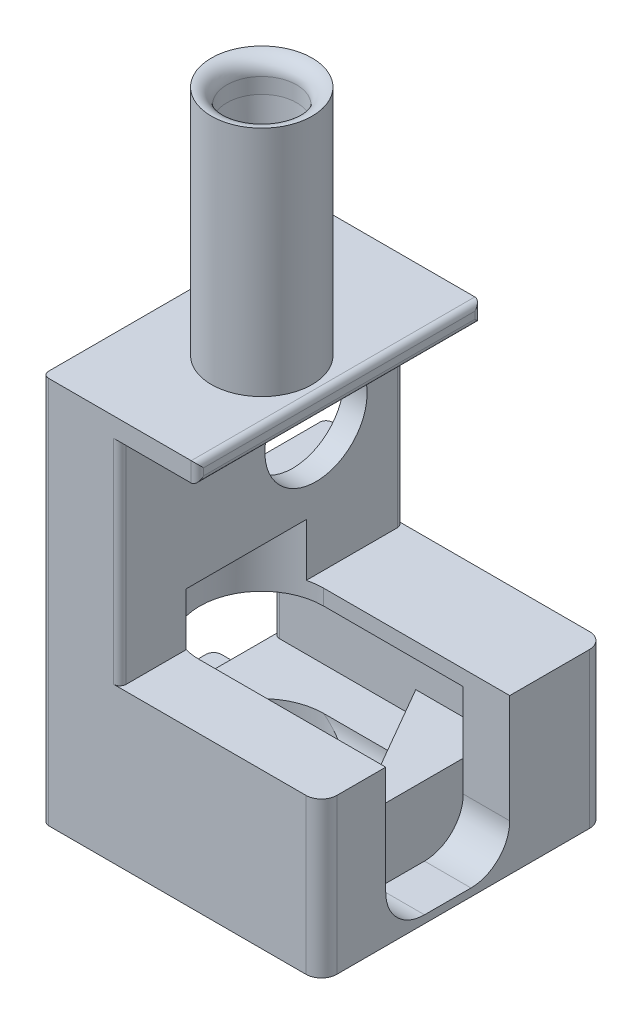
SolidWorks part; units mm, degrees
note: '?' marks a value the reader was unsure of.
ref_plane "Front Plane" through (0, 0, 0) normal (0, 0, 1) x (1, 0, 0)
ref_plane "Top Plane" through (0, 0, 0) normal (0, 1, 0) x (1, 0, 0)
ref_plane "Right Plane" through (0, 0, 0) normal (1, 0, 0) x (0, 0, -1)
sketch "Sketch1" plane through (0, 0, 0) normal (0, 1, 0) x (1, 0, 0)
  line L7 (-6, -6.5) -> (6, -6.5)
  line L8 (-6, -6.5) -> (-6, 6.5)
  line L9 (-6, 6.5) -> (6, 6.5)
  line L10 (6, -6.5) -> (6, 6.5)
  line L11 (-6, -6.5) -> (6, 6.5) construction
  line L12 (-6, 6.5) -> (6, -6.5) construction
  point P0 (0, 0)
  dimension "D1" = 12
  dimension "D3" = 13
extrude "Boss-Extrude1" add sketch "Sketch1" along normal blind 19
sketch "Sketch2" plane through (0, 0, 0) normal (0, -1, 0) x (1, 0, 0)
  circle A0 centre (0, 0) radius 4
  dimension "D1" = 8
extrude "Cut-Extrude1" cut sketch "Sketch2" against normal blind 16
ref_plane "Plane1" through (0, 2, 0) normal (0, -1, 0) x (-1, 0, 0)
sketch "Sketch3" plane through (0, 0, 0) normal (0, -1, 0) x (1, 0, 0)
  line L1 (6, 6.5) -> (6, -6.5) construction
  line L6 (6, -6.5) -> (-6, -6.5) construction
  line L10 (-6, -6.5) -> (-6, 6.5) construction
  line L11 (-6, 6.5) -> (6, 6.5) construction
  line L12 (6, 6.5) -> (6, -6.5)
  line L13 (6, -6.5) -> (-6, -6.5)
  line L14 (-6, -6.5) -> (-6, 6.5)
  line L15 (-6, 6.5) -> (6, 6.5)
extrude "Cut-Extrude2" cut sketch "Sketch3" against normal blind 6 from surface at -2 starting at plane "Plane1"
sketch "Sketch5" plane through (0, 19, 0) normal (0, 1, 0) x (1, 0, 0)
  line L0 (6, -6.5) -> (6, 6.5) construction
  line L1 (-6, -6.5) -> (6, -6.5)
  line L2 (-6, -6.5) -> (-6, 6.5)
  line L3 (-6, 6.5) -> (6, 6.5)
  line L4 (6, -6.5) -> (6, 6.5)
  line L5 (6, 6.5) -> (-6, 6.5) construction
extrude "Boss-Extrude2" add sketch "Sketch5" along normal blind 5
sketch "Sketch9" plane through (0, 24, 0) normal (0, 1, 0) x (1, 0, 0)
  circle A0 centre (0, 0) radius 1
  dimension "D1" = 2
fillet "Fillet1" radius 2 2 edges at (-6, 16, -6.5) (-6, 16, 6.5)
fillet "Fillet4" radius 2 2 edges at (-6, 1, -6.5) (-6, 1, 6.5)
ref_plane "Plane4" through (0, 0, 0) normal (0, 0, 1) x (1, 0, 0)
sketch "Sketch21" plane through (-6, 0, 0) normal (-1, 0, 0) x (0, 0, 1)
  line L0 (-4.5, 24) -> (-4.5, 8) construction
  line L1 (-4.5, 22) -> (-2, 22)
  line L2 (-4.5, 22) -> (-4.5, 14)
  line L3 (-4.5, 14) -> (-2, 14)
  line L4 (-2, 22) -> (-2, 14)
  line L5 (-4.5, 24) -> (4.5, 24) construction
  line L6 (0, 24) -> (0, 0) construction
  line L7 (-4.5, 0) -> (4.5, 0) construction
  line L8 (2, 22) -> (2, 14)
  line L9 (4.5, 14) -> (2, 14)
  line L10 (4.5, 22) -> (4.5, 14)
  line L11 (4.5, 22) -> (2, 22)
  line L12 (4.5, 8) -> (4.5, 24) construction
  line L13 (-4.5, 0) -> (4.5, 0)
  line L14 (-4.5, 0) -> (-4.5, 1.5)
  line L15 (-4.5, 1.5) -> (4.5, 1.5)
  line L16 (4.5, 0) -> (4.5, 1.5)
  line L17 (-4.5, 2) -> (-4.5, 0) construction
  line L18 (-4.5, 0) -> (4.5, 0) construction
  dimension "D1" = 2.5
  dimension "D2" = 2
  dimension "D3" = 8
  dimension "D4" = 1.5
extrude "Boss-Extrude4" add sketch "Sketch21" along normal blind 1.6
fillet "Fillet3" radius 0.5 4 edges at (-7.6, 22, 3.25) (-7.6, 18, 2) (-7.6, 14, 3.25) (-7.6, 18, 4.5)
fillet "Fillet7" radius 0.5 4 edges at (-7.6, 14, -3.25) (-7.6, 18, -4.5) (-7.6, 18, -2) (-7.6, 22, -3.25)
fillet "Fillet5" radius 0.5 2 edges at (-7.6, 0.75, -4.5) (-7.6, 0.75, 4.5)
sketch "Sketch23" plane through (0, 0, 0) normal (0, -1, 0) x (1, 0, 0)
  line L4 (-7.6, 4) -> (-7.6, -4)
  line L8 (-4, -6.5) -> (6, -6.5)
  line L9 (6, -6.5) -> (6, 6.5)
  line L10 (6, 6.5) -> (-4, 6.5)
  line L11 (-7.6, 4) -> (-7.6, -4)
  line L14 (-4, -6.5) -> (6, -6.5)
  line L15 (6, -6.5) -> (6, 6.5)
  line L16 (6, 6.5) -> (-4, 6.5)
  line L18 (-7.1, -4.5) -> (-6, -4.5)
  line L19 (-7.1, -4.5) -> (-6, -4.5)
  line L20 (-6, 4.5) -> (-7.1, 4.5)
  line L21 (-6, 4.5) -> (-7.1, 4.5)
  circle A0 centre (0, 0) radius 4 construction
  circle A1 centre (0, 0) radius 4
  arc A5 (-7.6, -4) -> (-7.1, -4.5) centre (-7.1, -4) ccw
  arc A6 (-7.6, -4) -> (-7.1, -4.5) centre (-7.1, -4) ccw
  arc A12 (-6, -4.5) -> (-4, -6.5) centre (-4, -4.5) ccw
  arc A22 (-6, -4.5) -> (-4, -6.5) centre (-4, -4.5) ccw
  arc A24 (-4, 6.5) -> (-6, 4.5) centre (-4, 4.5) ccw
  arc A25 (-4, 6.5) -> (-6, 4.5) centre (-4, 4.5) ccw
  arc A26 (-7.1, 4.5) -> (-7.6, 4) centre (-7.1, 4) ccw
  arc A27 (-7.1, 4.5) -> (-7.6, 4) centre (-7.1, 4) ccw
  dimension "D1" = 0
extrude "Boss-Extrude5" add sketch "Sketch23" along normal blind 1
sketch "Sketch25" plane through (6, 0, 0) normal (1, 0, 0) x (0, 0, -1)
  line L0 (6.5, 24) -> (6.5, 8) construction
  line L1 (-6.5, 8) -> (6.5, 8)
  line L2 (-6.5, 8) -> (-6.5, 11)
  line L3 (-6.5, 11) -> (6.5, 11)
  line L4 (6.5, 8) -> (6.5, 11)
  dimension "D1" = 3
sketch "Sketch26" plane through (0, 0, -6.5) normal (0, 0, -1) x (-1, 0, 0)
  line L0 (-6, 24) -> (-12, 24)
  line L3 (-12, 24) -> (-12, -1)
  line L4 (-12, -1) -> (-6, -1)
  line L5 (-6, -1) -> (-6, 2)
  line L6 (-6, 2) -> (-9, 2)
  line L7 (-9, 2) -> (-9, 8)
  line L8 (-9, 8) -> (-6, 8)
  line L9 (-6, 8) -> (-6, 11) construction
  line L10 (-6, 8) -> (-6, 11) construction
  line L11 (-6, 8) -> (-6, 24)
  line L12 (-6, 8) -> (4, 8) construction
  dimension "D2" = 3
  dimension "D3" = 3
extrude "Boss-Extrude6" add sketch "Sketch26" against normal through all
sketch "Sketch30" plane through (0, 24, 0) normal (0, 1, 0) x (1, 0, 0)
  line L0 (-6, 4.5) -> (-6, 8.15)
  line L1 (-6, 8.15) -> (12, 8.15)
  line L2 (12, 8.15) -> (12, 6.5)
  line L3 (12, 6.5) -> (-4, 6.5)
  line L5 (-4, 6.5) -> (-6, 6.5)
  line L6 (-6.6, 0) -> (6.6, 0) construction
  line L7 (-4, -6.5) -> (-6, -6.5) construction
  line L8 (12, -6.5) -> (-4, -6.5)
  line L9 (12, -8.15) -> (12, -6.5)
  line L10 (-6, -8.15) -> (12, -8.15)
  line L11 (-6, -4.5) -> (-6, -8.15)
  line L12 (12, -6.5) -> (12, 6.5) construction
  arc A0 (-4, 6.5) -> (-6, 4.5) centre (-4, 4.5) ccw construction
  arc A1 (-4, 6.5) -> (-6, 4.5) centre (-4, 4.5) ccw
  arc A2 (-4, -6.5) -> (-6, -4.5) centre (-4, -4.5) cw
  dimension "D1" = 1.65
extrude "Boss-Extrude7" add sketch "Sketch30" against normal through all
sketch "Sketch34" plane through (-6, 0, 0) normal (-1, 0, 0) x (0, 0, 1)
  line L0 (4.5, 2) -> (-4.5, 2) construction
  line L1 (-6.75, 8) -> (6.75, 8)
  line L2 (-6.75, 8) -> (-6.75, 2)
  line L3 (-6.75, 2) -> (6.75, 2)
  line L4 (6.75, 8) -> (6.75, 2)
  line L5 (0, 2) -> (0, 8) construction
  line L6 (-6.75, 5) -> (6.75, 5) construction
  line L7 (4.5, 8) -> (-4.5, 8) construction
  point P0 (0, 5)
  dimension "D1" = 13.5
extrude "Cut-Extrude5" cut sketch "Sketch34" against normal up to surface (15 mm away) up to face at (9, 5, 0)
hole_wizard "M2.5 Clearance Hole1" positions "Sketch32" profile "Sketch33" hole size "M2.5" standard "ANSI Metric"
sketch "Sketch32" plane through (12, 0, 0) normal (1, 0, 0) x (0, 0, -1)
  line L0 (-8.15, 24) -> (8.15, 24) construction
  point P0 (4.5, 17.5)
  dimension "D1" = 6.5
  dimension "D2" = 4.5
sketch "Sketch33" plane through (12, 17.5, -4.5) normal (0, 1, 0) x (0, 0, -1)
  line L0 (0, 0) -> (0, 20)
  line L1 (0, 20) -> (1.45, 19.1288)
  line L2 (1.45, 19.1288) -> (1.45, 0)
  line L5 (1.45, 0) -> (0, 0)
  line L10 (0, 20) -> (-1.45, 19.1288) construction
  line L11 (0, -6.35) -> (0, 107.95) construction
  dimension "Hole Dia." = 2.9
  dimension "Hole Depth" = 20
  dimension "Drill Angle" = 118
fillet "Fillet8" radius 0.4 3 edges at (-6, 11.5, 8.15) (-6, 5, -6.75) (-6, 5, 6.75)
sketch "Sketch31" plane through (0, 24, 0) normal (0, 1, 0) x (1, 0, 0)
  circle A0 centre (0, 0) radius 3.25
  circle A1 centre (0, 0) radius 2.25
  dimension "D1" = 6.5
  dimension "D2" = 1
extrude "Boss-Extrude8" add sketch "Sketch31" along normal blind 15
fillet "Fillet9" radius 1 1 edges at (12, 11.5, 8.15)
extrude "Cut-Extrude6" cut sketch "Sketch9" against normal through all contours A0
sketch "Sketch47" plane through (0, 39, 0) normal (0, 1, 0) x (1, 0, 0)
  circle A0 centre (0, 0) radius 2.25 construction
  circle A1 centre (0, 0) radius 2.25
sketch "Sketch42" plane through (12, 0, 0) normal (1, 0, 0) x (0, 0, -1)
  line L0 (-1.5, 11) -> (1.5, 11) construction
  line L1 (-1.5, 13.5) -> (1.5, 13.5)
  line L2 (-1.5, 8.5) -> (1.5, 8.5) construction
  line L3 (-4, 11) -> (-4, 2)
  line L4 (-1.5, -0.5) -> (1.5, -0.5)
  line L5 (4, 2) -> (4, 11)
  arc A0 (-1.5, 13.5) -> (-4, 11) centre (-1.5, 11) ccw
  arc A1 (4, 11) -> (1.5, 13.5) centre (1.5, 11) ccw
  arc A2 (-4, 2) -> (-1.5, -0.5) centre (-1.5, 2) ccw
  arc A3 (1.5, -0.5) -> (4, 2) centre (1.5, 2) ccw
  arc A4 (-4, 11) -> (-1.5, 8.5) centre (-1.5, 11) ccw construction
  arc A5 (1.5, 8.5) -> (4, 11) centre (1.5, 11) ccw construction
  circle A6 centre (4.5, 17.5) radius 1.45 construction
  point P18 (0, 11)
  point P21 (0, 8.5)
  dimension "D3" = 2.5
  dimension "D4" = 2.5
  dimension "D5" = 2.5
  dimension "D1" = 3
  dimension "D2" = 6.5
  dimension "D6" = 14
extrude "Cut-Extrude8" cut sketch "Sketch42" against normal blind 12
ref_plane "Plane6" through (0, 0, 0.05) normal (0, 0, 1) x (1, 0, 0)
sketch "Sketch43" plane through (0, 0, 0) normal (0, 0, 1) x (1, 0, 0)
  line L1 (-5.6, 24) -> (11, 24) construction
  line L2 (2.25, 24) -> (2.25, 37) construction
  line L4 (2.25, 39) -> (-2.25, 39) construction
  line L5 (-3.25, 37) -> (1.5, 37) construction
  line L6 (1.5, 37) -> (1.5, 24) construction
  line L7 (-3.25, 39) -> (-3.25, 24) construction
  line L8 (0, 39) -> (0, 24)
  line L9 (3.25, 24) -> (3.25, 39) construction
  line L10 (3.25, 24) -> (3.25, 39) construction
  line L11 (2.25, 39) -> (-2.25, 39) construction
  line L12 (3.25, 24) -> (-3.25, 24) construction
  line L13 (1.5, 24) -> (2.25, 24)
  line L14 (2.25, 24) -> (2.25, 37)
  line L15 (1.5, 37) -> (2.25, 37) construction
  line L16 (2.25, 37) -> (3.25, 37) construction
  line L17 (1.5, 37) -> (2.25, 37) construction
  line L18 (1.5, 24) -> (2.25, 37)
  dimension "D1" = 1
  dimension "D2" = 2
  dimension "D3" = 0.75
ref_axis "Axis1" through (0, 39, 0) along (0, -1, 0)?
ref_plane "Plane7" through (0, 0, 0) normal (-1, 0, 0) x (0, -1, 0)
ref_plane "Plane8" through (0.025, 0, 0.025) normal (-0.7071, 0, -0.7071) x (-0.7071, 0, 0.7071)
ref_axis "Axis3" through (0, 39, 0) along (0, -1, 0)?
revolve "Revolve1" add sketch "Sketch43" angle 360 about L8
ref_plane "Plane9" through (0, 2, 0) normal (0, 1, 0) x (1, 0, 0)
sketch "Sketch45" plane through (0, 2, 0) normal (0, 1, 0) x (1, 0, 0)
  line L0 (-6, 8.15) -> (12, 8.15) construction
  line L1 (-5.456, 3.15) -> (-7.2746, 0) construction
  line L2 (-5.456, -3.15) -> (-3.6373, -6.3) construction
  line L3 (-3.6373, -6.3) -> (0, -6.3) construction
  line L4 (3.6373, -6.3) -> (7.2746, 0)
  line L5 (7.2746, 0) -> (3.6373, 6.3)
  line L6 (0, 6.3) -> (-3.6373, 6.3) construction
  line L8 (3.6373, -6.3) -> (9, -6.3)
  line L9 (9, -6.3) -> (9, 6.3)
  line L10 (9, 6.3) -> (3.6373, 6.3)
  line L11 (9, -6.75) -> (9, -4) construction
  line L12 (3.6373, 6.3) -> (0, 6.3) construction
  line L13 (0, -6.3) -> (3.6373, -6.3) construction
  line L14 (-3.6373, 6.3) -> (-5.456, 3.15) construction
  line L15 (-7.2746, 0) -> (-5.456, -3.15) construction
  arc A0 (-5.456, 3.15) -> (-5.456, -3.15) centre (0, 0) ccw construction
  arc A1 (5.456, 3.15) -> (0, 6.3) centre (0, 0) ccw construction
  arc A2 (0, -6.3) -> (5.456, -3.15) centre (0, 0) ccw construction
  arc A3 (5.456, -3.15) -> (5.456, 3.15) centre (0, 0) ccw construction
  arc A4 (-5.456, -3.15) -> (0, -6.3) centre (0, 0) ccw construction
  arc A5 (0, 6.3) -> (-5.456, 3.15) centre (0, 0) ccw construction
  dimension "D1" = 12.6
extrude "Boss-Extrude9" add sketch "Sketch45" along normal blind 4.5 from surface at -2.5 starting at face at (7.927, -0.5, 0)
fillet "Fillet10" radius 1 1 edges at (0, 39, 2.25)
sketch "Sketch48" plane through (0, 0, 8.15) normal (0, 0, 1) x (1, 0, 0)
  line L1 (12, 24) -> (0, 24)
  line L2 (12, 24) -> (12, 9)
  line L3 (12, 9) -> (0, 9)
  line L4 (0, 24) -> (0, 9)
  dimension "D1" = 15
  dimension "D2" = 12
extrude "Cut-Extrude9" cut sketch "Sketch48" against normal up to surface (16.3 mm away) up to face at (3, 11.5, -8.15)
sketch "Sketch49" plane through (0, 0, 0) normal (1, 0, 0) x (0, 0, -1)
  line L0 (7.4445, 22.6) -> (8.15, 22.6)
  line L1 (10.389, 17.5) -> (8.9167, 20.05) construction
  line L2 (7.4445, 22.6) -> (1.5555, 22.6)
  line L3 (1.5555, 22.6) -> (-1.389, 17.5)
  line L4 (-1.389, 17.5) -> (1.5555, 12.4)
  line L5 (1.5555, 12.4) -> (7.4445, 12.4)
  line L6 (7.4445, 12.4) -> (8.9167, 14.95) construction
  line L7 (8.15, 9) -> (8.15, 24) construction
  line L8 (7.4445, 12.4) -> (8.15, 12.4)
  line L9 (8.15, 12.4) -> (8.15, 22.6)
  line L10 (8.9167, 20.05) -> (7.4445, 22.6) construction
  line L11 (8.9167, 14.95) -> (10.389, 17.5) construction
  line L12 (8.15, 24) -> (3.25, 24) construction
  arc A0 (4.5, 22.6) -> (4.5, 12.4) centre (4.5, 17.5) ccw construction
  arc A1 (8.9167, 20.05) -> (4.5, 22.6) centre (4.5, 17.5) ccw construction
  arc A2 (8.9167, 14.95) -> (8.9167, 20.05) centre (4.5, 17.5) ccw construction
  arc A3 (4.5, 12.4) -> (8.9167, 14.95) centre (4.5, 17.5) ccw construction
  dimension "D1" = 10.2
extrude "Cut-Extrude10" cut sketch "Sketch49" against normal blind 5.5 from offset 2.5 offset against normal yes
sketch "Sketch50" plane through (0, 0, 0) normal (1, 0, 0) x (0, 0, -1)
  line L0 (8.15, 9) -> (8.15, 24) construction
  line L1 (-8.15, 24) -> (8.15, 24)
  line L2 (-8.15, 24) -> (-8.15, 16)
  line L3 (-8.15, 16) -> (8.15, 16)
  line L4 (8.15, 24) -> (8.15, 16)
  line L5 (-4, 16) -> (-0.5229, 16) construction
extrude "Cut-Extrude11" cut sketch "Sketch50" against normal up to vertex (1 mm away)
sketch "Sketch56" plane through (0, 24, 0) normal (0, 1, 0) x (1, 0, 0)
  line L0 (-1, -8.15) -> (-1, -0.65)
  line L1 (-1, -3.0923) -> (-1, -8.15) construction
  line L2 (-1, -0.65) -> (-4, -8.15)
  line L3 (-5.6, -8.15) -> (-1, -8.15) construction
  line L4 (-4, -8.15) -> (-1, -8.15)
  dimension "D1" = 7.5
  dimension "D2" = 3
extrude "Cut-Extrude13" cut sketch "Sketch56" against normal up to surface (8 mm away) up to face at (-0.501, 16, 6.0512)
sketch "Sketch51" plane through (-1, 0, 0) normal (1, 0, 0) x (0, 0, -1)
  line L1 (-4.65, 24) -> (-7.15, 24)
  line L2 (-4.65, 24) -> (-4.65, 16)
  line L3 (-4.65, 16) -> (-7.15, 16)
  line L4 (-7.15, 24) -> (-7.15, 16)
  line L5 (-8.15, 24) -> (-8.15, 16) construction
  line L6 (1.118, 24) -> (-0.65, 24) construction
  line L7 (-8.15, 16) -> (-4, 16) construction
  dimension "D1" = 2.5
  dimension "D2" = 1
extrude "Boss-Extrude10" add sketch "Sketch51" along normal blind 5 and the other way up to surface other way up to face at (-2.1503, 20.5714, 3.5258)
sketch "Sketch54" plane through (0, 0, 4.65) normal (0, 0, -1) x (-1, 0, 0)
  line L0 (1.35, 24) -> (1.35, 19.75) construction
  line L1 (-4, 24) -> (2.6, 24) construction
  line L2 (-4, 16) -> (0, 16) construction
  line L4 (2.6, 16) -> (2.6, 24) construction
  line L5 (1.35, 22.75) -> (2.6, 22.75)
  line L6 (2.6, 22.75) -> (2.6, 20.25)
  line L7 (2.6, 20.25) -> (1.35, 20.25) construction
  line L8 (2.6, 24) -> (-4, 24) construction
  line L9 (0, 16) -> (-4, 16) construction
  line L10 (1.35, 19.75) -> (2.6, 19.75) construction
  line L11 (2.6, 16) -> (2.6, 24) construction
  line L12 (2.6, 19.75) -> (2.6, 17.25)
  line L13 (2.6, 17.25) -> (1.35, 17.25)
  line L14 (0.1, 18.5) -> (0.1, 21.5)
  line L15 (1.35, 19.75) -> (1.35, 17.25) construction
  line L16 (1.35, 17.25) -> (1.35, 16) construction
  line L17 (2.6, 20.25) -> (2.6, 19.75)
  arc A0 (1.35, 22.75) -> (0.1, 21.5) centre (1.35, 21.5) ccw
  arc A1 (2.6, 21.5) -> (1.35, 22.75) centre (1.35, 21.5) ccw construction
  arc A2 (1.35, 20.25) -> (2.6, 21.5) centre (1.35, 21.5) ccw construction
  arc A3 (0.1, 18.5) -> (1.35, 17.25) centre (1.35, 18.5) ccw
  arc A4 (2.6, 18.5) -> (1.35, 19.75) centre (1.35, 18.5) ccw construction
  arc A5 (1.35, 17.25) -> (2.6, 18.5) centre (1.35, 18.5) ccw construction
  arc A6 (0.1, 21.5) -> (1.35, 20.25) centre (1.35, 21.5) ccw construction
  arc A7 (1.35, 19.75) -> (0.1, 18.5) centre (1.35, 18.5) ccw construction
  dimension "D2" = 2.5
  dimension "D5" = 2.5
  dimension "D1" = 1.25
  dimension "D3" = 2.5
  dimension "D4" = 2.5
extrude "Cut-Extrude12" cut sketch "Sketch54" against normal up to surface (2.5 mm away) up to face at (0.16, 19.2, 7.15)
sketch "Sketch57" plane through (0, 24, 0) normal (0, 1, 0) x (1, 0, 0)
  line L0 (-2.6, -4.65) -> (-3.6, -7.15)
  line L1 (-3.6, -7.15) -> (-2.6, -7.15)
  line L2 (-3.6, -7.15) -> (4, -7.15) construction
  line L3 (-2.6, -7.15) -> (-2.6, -4.65)
  line L4 (-2.6, -7.15) -> (-2.6, -4.65) construction
extrude "Cut-Extrude14" cut sketch "Sketch57" against normal up to surface (5.5 mm away) from surface at -1.25 up to face at (-1.975, 17.25, 5.9) starting at face at (-1.975, 22.75, 5.9)
sketch "Sketch59" plane through (0, 24, 0) normal (0, -1, 0) x (1, 0, 0)
  line L1 (-1, -1.118) -> (-1, -8.15)
  line L2 (-1, -8.15) -> (4, -8.15)
  line L3 (4, -8.15) -> (4, 8.15)
  line L4 (4, 8.15) -> (-1.1331, 8.15)
  line L5 (-1.1331, 0.9828) -> (-1.8177, 2.6942) construction
  line L6 (-5.6, 8.15) -> (-4, 8.15) construction
  line L8 (-1.1331, 0.9828) -> (-4, 8.15)
  line L9 (-4, 8.15) -> (-1.1331, 8.15)
  arc A0 (-1.1331, 0.9828) -> (-1, -1.118) centre (0, 0) cw
  arc A6 (-1, -1.118) -> (-1.1331, 0.9828) centre (0, 0) ccw construction
  dimension "D1" = 5
extrude "Boss-Extrude11" add sketch "Sketch59" along normal up to surface (1.25 mm away) up to face at (-2.225, 22.75, 5.9)
sketch "Sketch58" plane through (-1, 0, 0) normal (1, 0, 0) x (0, 0, -1)
  circle A0 centre (4.5, 17.5) radius 3.3
  circle A1 centre (4.5, 17.5) radius 1.45 construction
  dimension "D1" = 6.6
extrude "Cut-Extrude16" cut sketch "Sketch58" against normal up to surface (6.6 mm away) up to face at (-7.6, 0.25, 0)
sketch "Sketch63" plane through (-1, 0, 0) normal (1, 0, 0) x (0, 0, -1)
  circle A0 centre (4.5, 17.5) radius 5
  dimension "D1" = 10
ref_plane "Plane10" through (0, 16, 7.15) normal (1, 0, 0) x (0, 0, -1)
sketch "Sketch65" plane through (0, 16, 0) normal (0, 1, 0) x (1, 0, 0)
  line L0 (-4, -8.15) -> (0, -8.15) construction
  line L1 (-1, -8.15) -> (0, -8.15)
  line L2 (-1, -8.15) -> (-1, 8.15)
  line L3 (-1, 8.15) -> (0, 8.15)
  line L4 (0, -8.15) -> (0, 8.15)
  line L5 (-1, 8.15) -> (0, 8.15) construction
  line L6 (-1, 3.873) -> (-1, 7.4394) construction
  line L7 (0, 4) -> (0, 8.15) construction
extrude "Cut-Extrude17" cut sketch "Sketch65" against normal up to surface (7 mm away) up to face at (6, 9, -6.075)
sketch "Sketch67" plane through (0, 0, -8.15) normal (0, 0, -1) x (-1, 0, 0)
  line L12 (1, 22.75) -> (1, 9)
  line L13 (1, 9) -> (-12, 9)
  line L14 (-12, 9) -> (-12, -1)
  line L15 (-12, -1) -> (6, -1)
  line L16 (6, -1) -> (6, 12.4)
  line L17 (6, 12.4) -> (2.5, 12.4)
  line L18 (2.5, 12.4) -> (2.5, 22.6)
  line L19 (2.5, 22.6) -> (6, 22.6)
  line L20 (6, -1) -> (6, 12.4)
  line L21 (6, 24) -> (-4, 24)
  line L22 (-4, 24) -> (-4, 22.75)
  line L23 (-4, 22.75) -> (1, 22.75)
  line L24 (1, 22.75) -> (1, 9)
  line L25 (1, 9) -> (-12, 9)
  line L27 (-12, -1) -> (6, -1)
  line L29 (6, 12.4) -> (2.5, 12.4)
  line L30 (2.5, 12.4) -> (2.5, 22.6)
  line L31 (2.5, 22.6) -> (6, 22.6)
  line L33 (6, 24) -> (-4, 24)
  line L34 (-4, 24) -> (-4, 22.75)
  line L35 (-4, 22.75) -> (1, 22.75)
  line L36 (-12, 9) -> (-12, -1)
  line L37 (6, 22.6) -> (6, 24)
  line L38 (6, 22.6) -> (6, 24)
  dimension "D1" = 0
extrude "Boss-Extrude12" add sketch "Sketch67" along normal blind 2
fillet "Fillet11" radius 1 1 edges at (12, 4, -10.15)
sketch "Sketch68" plane through (0, 16, 0) normal (0, -1, 0) x (1, 0, 0)
  line L0 (-1, 7.15) -> (4, 7.15) construction
  line L1 (4, 4.65) -> (-2.6, 4.65)
  line L2 (4, 4.65) -> (4, 7.15)
  line L3 (4, 7.15) -> (-2.6, 7.15)
  line L4 (-2.6, 4.65) -> (-2.6, 7.15) construction
  line L5 (-2.6, 7.15) -> (-3.6, 7.15)
  line L6 (-3.6, 7.15) -> (-3.3097, 6.4242)
  line L7 (-3.3097, 6.4242) -> (-2.6, 4.65)
  line L8 (-1.1331, 0.9828) -> (-4, 8.15) construction
extrude "Cut-Extrude18" cut sketch "Sketch68" against normal up to surface (6.75 mm away) up to face at (0.873, 22.75, 1.9627)
sketch "Sketch69" plane through (0, 16, 0) normal (0, 1, 0) x (1, 0, 0)
  line L0 (-4, -8.15) -> (-1, -8.15)
  line L1 (-1, -8.15) -> (-1, -0.65)
  line L2 (-1, -0.65) -> (-4, -8.15)
  line L3 (-1, -3.873) -> (-1, -8.15) construction
extrude "Boss-Extrude13" add sketch "Sketch69" along normal up to surface (6.75 mm away) up to face at (0.5717, 22.75, -0.6621)
fillet "Fillet12" radius 0.4 2 edges at (-6, 23.3, -10.15) (-6, 5.7, -10.15)
fillet "Fillet13" radius 0.4 6 edges at (4, 24, -1) (4, 22.75, -1) (-1, 15.875, -10.15) (-1, 15.875, 8.15) (4, 23.375, -10.15) (4, 23.375, 8.15)
sketch "Sketch74" plane through (-1, 0, 0) normal (1, 0, 0) x (0, 0, -1)
  line L0 (1.5555, 12.4) -> (3.1225, 12.4)
  line L1 (3.1225, 12.4) -> (3.873, 12.4)
  line L2 (3.873, 9) -> (3.873, 14.2601) construction
  line L3 (3.873, 12.4) -> (3.873, 14.2601)
  line L4 (1.5555, 12.4) -> (-0.5229, 16)
  line L5 (-3.873, 16) -> (1.5606, 16) construction
  line L6 (-0.5229, 16) -> (1.5606, 16)
  line L7 (1.5555, 12.4) -> (-0.5229, 16) construction
  arc A0 (3.873, 14.2601) -> (1.5606, 16) centre (4.5, 17.5) cw
extrude "Boss-Extrude18" add sketch "Sketch74" against normal up to surface (1.5 mm away) up to face at (-2.5, 17.329, -4.0241)
sketch "Sketch75" plane through (-1, 0, 0) normal (1, 0, 0) x (0, 0, -1)
  line L0 (1.5555, 12.4) -> (-3.873, 12.4)
  line L2 (-3.873, 12.4) -> (-3.873, 16)
  line L3 (-3.873, 16) -> (-0.5229, 16)
  line L4 (-0.5229, 16) -> (1.5555, 12.4)
  line L5 (1.5555, 12.4) -> (3.873, 12.4) construction
extrude "Boss-Extrude19" add sketch "Sketch75" against normal up to surface (2.9657 mm away)
equation "\"D5@Sketch54\"=\"D2@Sketch54\""
equation "\"D4@Sketch54\"=\"D3@Sketch54\""
